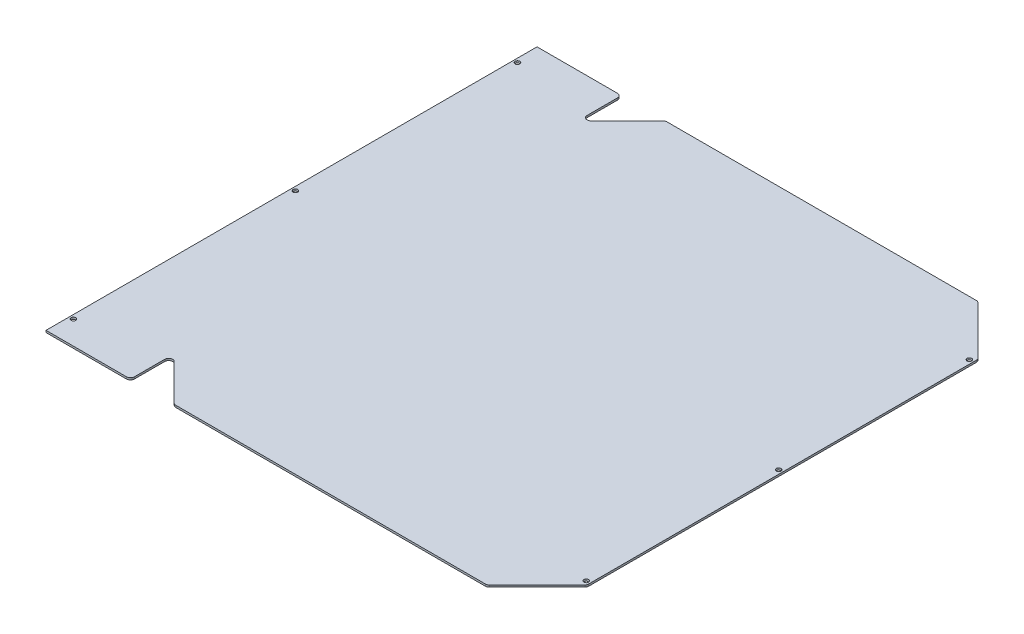
SolidWorks part; units mm, degrees
material "PC High Viscosity"
ref_plane "Front Plane" through (0, 0, 0) normal (0, 0, 1) x (1, 0, 0)
ref_plane "Top Plane" through (0, 0, 0) normal (0, 1, 0) x (1, 0, 0)
ref_plane "Right Plane" through (0, 0, 0) normal (1, 0, 0) x (0, 0, -1)
sketch "Sketch1" plane through (0, 0, 0) normal (0, 1, 0) x (1, 0, 0)
  line L0 (158.75, 199.39) -> (199.39, 158.75)
  line L1 (-199.39, 199.39) -> (199.39, 199.39)
  line L2 (-199.39, 199.39) -> (-199.39, -199.39)
  line L3 (-199.39, -199.39) -> (199.39, -199.39)
  line L4 (199.39, 199.39) -> (199.39, -199.39)
  line L5 (158.75, -199.39) -> (199.39, -158.75)
  line L6 (-130.81, 199.39) -> (-130.81, 163.83)
  line L7 (-130.81, 163.83) -> (-95.25, 199.39)
  line L9 (-130.81, -199.39) -> (-130.81, -163.83)
  line L10 (-130.81, -163.83) -> (-95.25, -199.39)
  point P0 (0, 0)
  point P6 (-199.39, 0)
  point P7 (196.215, 0)
  point P9 (0, 199.39)
  point P13 (-196.215, 0)
  point P17 (0, 0)
  point P19 (-125.73, 142.383)
  point P22 (0, 0)
  point P27 (-196.215, -180.34)
  point P28 (196.215, 154.94)
  point P29 (196.215, -156.21)
  point P30 (-196.215, 180.34)
  dimension "D4" = 3.175
  dimension "D9" = 40.64
  dimension "D11" = 35.56
  dimension "D6" = 19.05
  dimension "D2" = 398.78
  dimension "D3" = 398.78
  dimension "D5" = 44.45
  dimension "D7" = 19.05
  dimension "D8" = 45
  dimension "D10" = 68.58
  dimension "D12" = 43.18
  dimension "D13" = 3.175
  dimension "D14" = 3.175
  dimension "D15" = 45
extrude "Boss-Extrude1" add sketch "Sketch1" against normal blind 1.5875
hole_wizard "#6 Clearance Hole1" positions "Sketch4" profile "Sketch5" hole size "#6" standard "ANSI Inch" end condition through all
sketch "Sketch4" plane through (0, -1.5875, 0) normal (0, -1, 0) x (-1, 0, 0)
  point P0 (196.215, 180.34)
  point P3 (196.215, -180.34)
  point P6 (-196.215, -156.21)
  point P9 (-196.215, 154.94)
  point P12 (196.215, 0)
  point P14 (-196.215, 0)
  point P17 (0, 0)
  point P19 (0, 0)
sketch "Sketch5" plane through (-196.215, -1.5875, -180.34) normal (1, 0, 0) x (0, 0, -1)
  line L0 (0, 0) -> (0, 1.5875)
  line L1 (0, 1.5875) -> (1.8986, 1.5875)
  line L2 (1.8986, 1.5875) -> (1.8986, 0)
  line L5 (1.8986, 0) -> (0, 0)
  line L11 (0, -6.35) -> (0, 107.95) construction
  dimension "Thru Hole Dia." = 3.7973
  dimension "Thru Hole Depth" = 1.5875
fillet "Fillet1" radius 3.175 10 edges at (158.75, -0.7937, -199.39) (199.39, -0.7937, -158.75) (199.39, -0.7937, 158.75) (158.75, -0.7937, 199.39) (-130.81, -0.7937, 163.83) (-130.81, -0.7937, 199.39) (-95.25, -0.7937, 199.39) (-95.25, -0.7937, -199.39) (-130.81, -0.7937, -199.39) (-130.81, -0.7937, -163.83)
